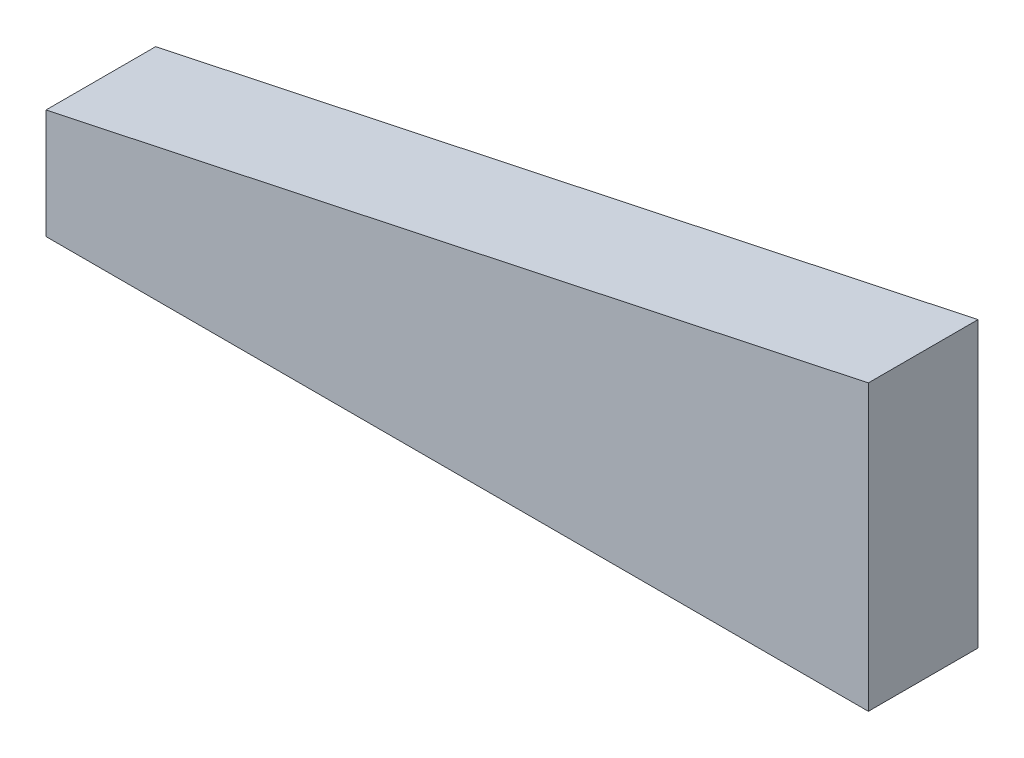
SolidWorks part; units mm, degrees
ref_plane "Front Plane" through (0, 0, 0) normal (0, 0, 1) x (1, 0, 0)
ref_plane "Top Plane" through (0, 0, 0) normal (0, 1, 0) x (1, 0, 0)
ref_plane "Right Plane" through (0, 0, 0) normal (1, 0, 0) x (0, 0, -1)
sketch "Sketch1" plane through (0, 0, 0) normal (0, 1, 0) x (1, 0, 0)
  line L1 (-75, -10) -> (75, -10)
  line L2 (-75, -10) -> (-75, 10)
  line L3 (-75, 10) -> (75, 10)
  line L4 (75, -10) -> (75, 10)
  line L5 (-75, -10) -> (75, 10) construction
  line L6 (-75, 10) -> (75, -10) construction
  point P0 (0, 0)
  dimension "D1" = 20
  dimension "D2" = 150
extrude "Boss-Extrude1" add sketch "Sketch1" along normal mid plane 20
sketch "Sketch2" plane through (0, 0, 0) normal (0, 0, 1) x (1, 0, 0)
  line L0 (-75, 10) -> (75, 10)
  line L1 (75, 10) -> (75, -10) construction
  line L2 (-75, 10) -> (75, 10) construction
  line L3 (75, 10) -> (75, 41.8835)
  line L4 (75, 41.8835) -> (-75, 10)
  dimension "D1" = 12
extrude "Boss-Extrude2" add sketch "Sketch2" along normal mid plane 20
